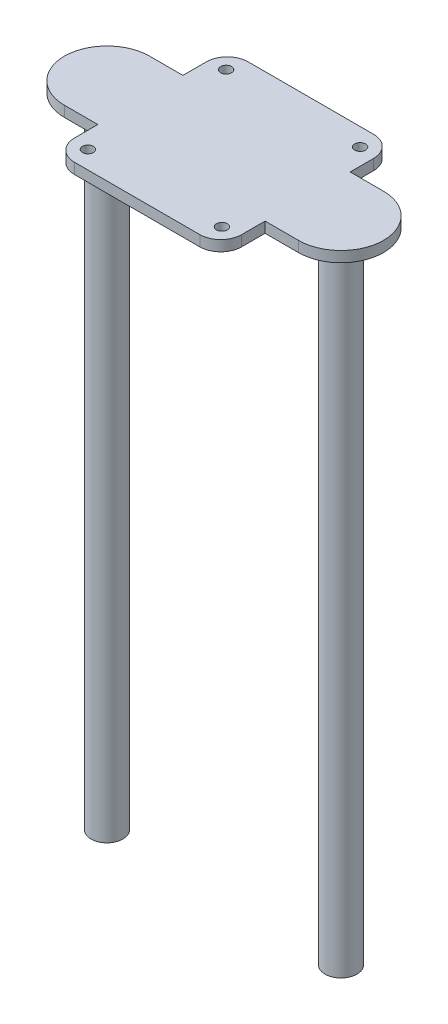
SolidWorks part; units mm, degrees
ref_plane "Front Plane" through (0, 0, 0) normal (0, 0, 1) x (1, 0, 0)
ref_plane "Top Plane" through (0, 0, 0) normal (0, 1, 0) x (1, 0, 0)
ref_plane "Right Plane" through (0, 0, 0) normal (1, 0, 0) x (0, 0, -1)
sketch "Sketch1" plane through (0, 0, 0) normal (0, 1, 0) x (1, 0, 0)
  line L0 (-27.94, 0) -> (27.94, 0) construction
  line L1 (-14.9694, 20.75) -> (14.9694, 20.75)
  line L2 (-19.9694, 15.75) -> (-19.9694, -15.75)
  line L3 (-14.9694, -20.75) -> (14.9694, -20.75)
  line L4 (19.9694, 15.75) -> (19.9694, -15.75)
  line L5 (-19.9694, 20.75) -> (19.9694, -20.75) construction
  line L6 (-19.9694, -20.75) -> (19.9694, 20.75) construction
  line L7 (-16, 16.5) -> (16, 16.5) construction
  line L8 (-16, 16.5) -> (-16, -16.5) construction
  line L9 (-16, -16.5) -> (16, -16.5) construction
  line L10 (16, 16.5) -> (16, -16.5) construction
  line L11 (-16, 16.5) -> (16, -16.5) construction
  line L12 (-16, -16.5) -> (16, 16.5) construction
  line L13 (-27.94, -10.16) -> (27.94, -10.16)
  line L14 (-27.94, 10.16) -> (27.94, 10.16)
  circle A0 centre (-16, 16.5) radius 1.3
  circle A1 centre (16, 16.5) radius 1.3
  circle A2 centre (16, -16.5) radius 1.3
  circle A3 centre (-16, -16.5) radius 1.3
  arc A4 (-19.9694, 15.75) -> (-14.9694, 20.75) centre (-14.9694, 15.75) cw
  arc A5 (19.9694, -15.75) -> (14.9694, -20.75) centre (14.9694, -15.75) cw
  arc A6 (19.9694, 15.75) -> (14.9694, 20.75) centre (14.9694, 15.75) ccw
  arc A7 (-19.9694, -15.75) -> (-14.9694, -20.75) centre (-14.9694, -15.75) ccw
  circle A8 centre (-27.94, 0) radius 3.81
  circle A9 centre (27.94, 0) radius 3.81
  arc A10 (-27.94, -10.16) -> (-27.94, 10.16) centre (-27.94, 0) cw
  arc A11 (27.94, -10.16) -> (27.94, 10.16) centre (27.94, 0) ccw
  point P2 (0, 0)
  point P7 (0, 0)
  dimension "D3" = 2.6
  dimension "D4" = 5
  dimension "D6" = 7.62
  dimension "D1" = 32
  dimension "D2" = 33
  dimension "D5" = 55.88
  dimension "D7" = 10.16
  dimension "D8" = 10.16
extrude "Boss-Extrude1" add sketch "Sketch1" along normal blind 2.54 contours A10 L13 L2 L14 A8 | L14 L2 L13 L4 | L2 A7 L3 A5 L4 L13 A2 A3 | L4 A6 L1 A4 L2 L14 A0 A1 | L13 A11 L14 L4 A9 | A8 | A9 region at (0, 0, -15.3157) region at (0, 0, 0) region at (-20.2418, 0, 0) region at (23.9547, 0, -9.8877) region at (0, 0, 15.3157) region at (-27.94, 0, 0) region at (27.94, 0, 0)
extrude "Boss-Extrude2" add sketch "Sketch1<3>" against normal blind 152.4 contours A9 | A8
sketch "Sketch1<3>" plane through (0, 0, 0) normal (0, 1, 0) x (1, 0, 0) same geometry as "Sketch1"
